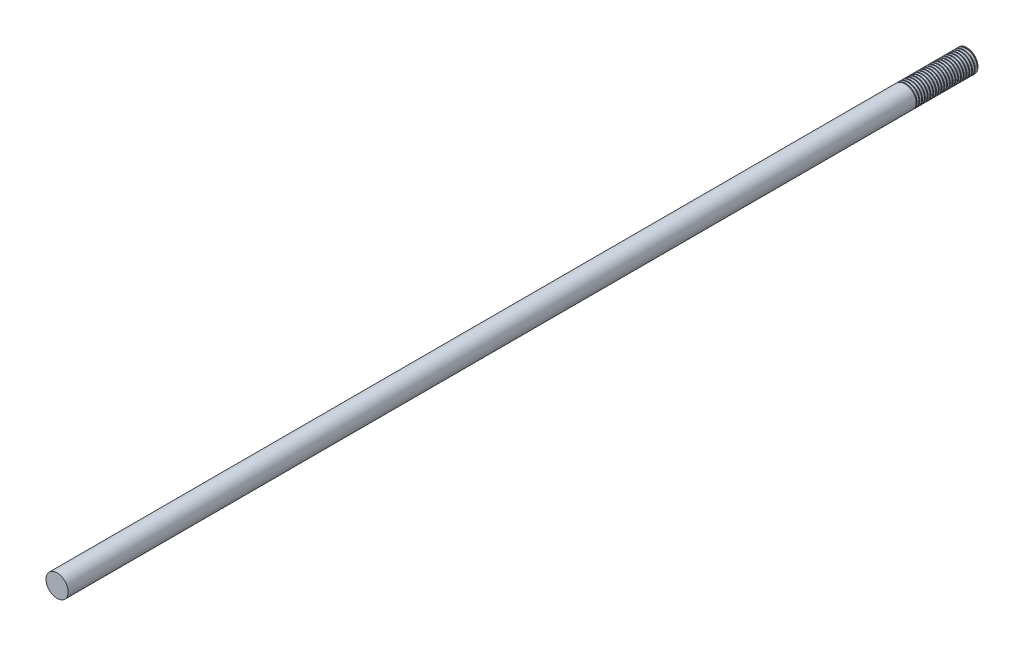
SolidWorks part; units mm, degrees
ref_plane "Front Plane" through (0, 0, 0) normal (0, 0, 1) x (1, 0, 0)
ref_plane "Top Plane" through (0, 0, 0) normal (0, 1, 0) x (1, 0, 0)
ref_plane "Right Plane" through (0, 0, 0) normal (1, 0, 0) x (0, 0, -1)
sketch "Sketch1" plane through (0, 0, 0) normal (0, 0, 1) x (1, 0, 0)
  circle A0 centre (0, 0) radius 3
  dimension "D1" = 6
extrude "Boss-Extrude1" add sketch "Sketch1" along normal blind 246
thread "Thread1" pitch 0.25 method cut profile "Thread Profile1" start angle 0, offset 0, length 17, pitch 0.75, diameter 6
ref_plane "Plane1" through (3, 0, 0) normal (0, -1, 0) x (1, 0, 0)
sketch "Thread Profile1" plane through (3, 0, 0) normal (0, -1, 0) x (1, 0, 0)
  line L0 (0, 0) -> (0, 0.25) construction
  line L11 (0, 0) -> (0, 0.2187)
  line L12 (0, 0.2187) -> (-0.1353, 0.1406)
  line L13 (-0.1353, 0.1406) -> (-0.1353, 0.0781)
  line L15 (-0.1353, 0.0781) -> (0, 0)
  line L17 (-0.1353, 0.1094) -> (0, 0.1094) construction
  point P2 (0, 0)
  dimension "Pitch" = 0.25
  dimension "Profile_Angle" = 60
  dimension "Profile_Land" = 0.0625
  dimension "Profile_Height" = 0.1353
